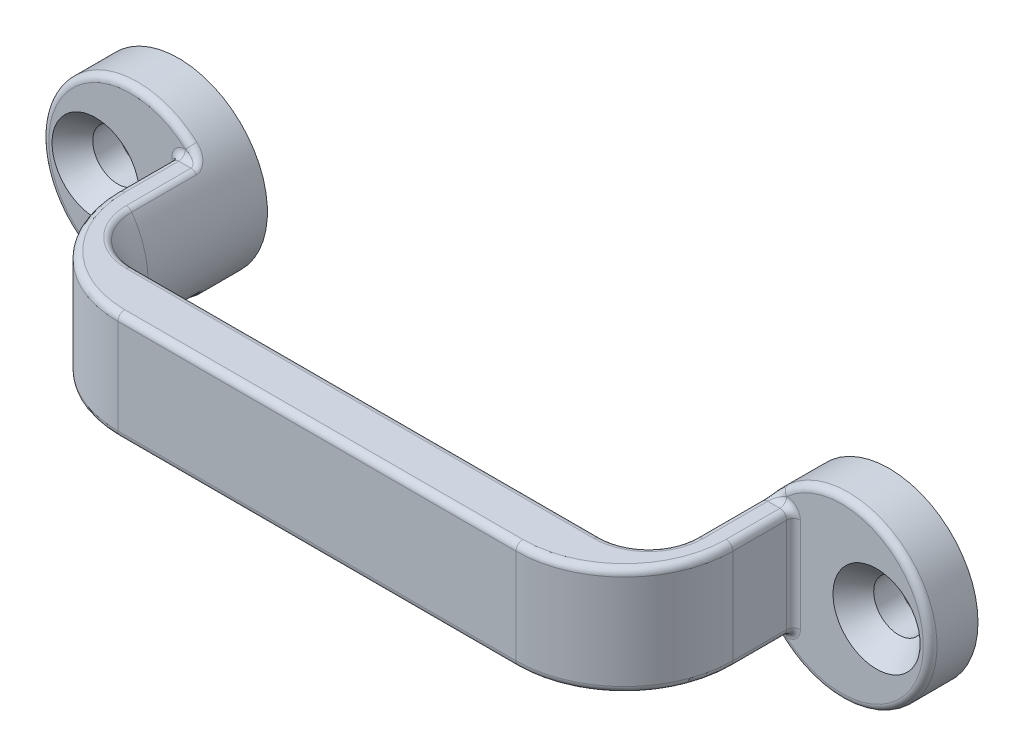
SolidWorks part; units mm, degrees
ref_plane "Front Plane" through (0, 0, 0) normal (0, 0, 1) x (1, 0, 0)
ref_plane "Top Plane" through (0, 0, 0) normal (0, 1, 0) x (1, 0, 0)
ref_plane "Right Plane" through (0, 0, 0) normal (1, 0, 0) x (0, 0, -1)
sketch "Sketch1" plane through (0, 0, 0) normal (0, 0, 1) x (1, 0, 0)
  line L0 (-28.575, 0) -> (28.575, 0) construction
  line L1 (26, 0) -> (-26, 0) construction
  line L2 (0, 3.9688) -> (0, -3.9688)
  circle A0 centre (-28.575, 0) radius 1.6383
  circle A1 centre (28.575, 0) radius 1.6383
  circle A2 centre (26, 0) radius 6.5
  circle A3 centre (-26, 0) radius 6.5
  dimension "Screw Size" = 3.2766
  dimension "Base Dia" = 13
  dimension "A" = 57.15
  dimension "Overall" = 65
  dimension "Height" = 7.9375
sketch "Sketch2" plane through (0, 0, 0) normal (0, 1, 0) x (1, 0, 0)
  line L0 (-19.5, 0) -> (-19.5, -8.7312)
  line L1 (-17.1188, -11.1125) -> (17.1188, -11.1125)
  line L2 (19.5, -8.7312) -> (19.5, 0)
  line L3 (-22.5, 0) -> (-22.5, -7.9375)
  line L4 (-14.5625, -15.875) -> (14.5625, -15.875)
  line L5 (22.5, -7.9375) -> (22.5, 0)
  line L6 (0, 0) -> (0, -15.875) construction
  line L7 (-28.575, 0) -> (28.575, 0) construction
  line L8 (-32.5, 0) -> (-19.5, 0) construction
  line L9 (19.5, 0) -> (32.5, 0) construction
  line L10 (-22.5, 0) -> (-19.5, 0)
  line L11 (19.5, 0) -> (22.5, 0)
  arc A0 (-22.5, -7.9375) -> (-14.5625, -15.875) centre (-14.5625, -7.9375) ccw
  arc A1 (14.5625, -15.875) -> (22.5, -7.9375) centre (14.5625, -7.9375) ccw
  arc A2 (-19.5, -8.7312) -> (-17.1188, -11.1125) centre (-17.1188, -8.7312) ccw
  arc A3 (17.1188, -11.1125) -> (19.5, -8.7312) centre (17.1188, -8.7312) ccw
  point P18 (-22.5, -15.875)
  point P23 (22.5, -15.875)
  dimension "D4" = 7.9375
  dimension "D5" = 2.3813
  dimension "Projection" = 15.875
  dimension "Handle lenght" = 44.9999
  dimension "Width" = 4.7625
extrude "Extrude1" add sketch "Sketch2" against normal up to vertex (3.9688 mm away) and the other way up to vertex (3.9688 mm away) up to point (0, -3.9688, 0) other way up to point (0, 3.9688, 0)
sketch "Sketch6" plane through (0, 0, 0) normal (0, 0, -1) x (-1, 0, 0)
  line L0 (19.5, -3.9688) -> (22.5, -3.9688) construction
  line L1 (19.5, 3.9688) -> (22.5, 3.9688) construction
  line L2 (17.8523, -3.9688) -> (20.8523, -3.9687)
  line L3 (17.8523, 3.9688) -> (20.8523, 3.9688)
  line L4 (17.8523, 3.9688) -> (17.8523, -3.9688)
  circle A0 centre (26, 0) radius 6.5 construction
  arc A1 (20.8523, 3.9688) -> (20.8523, -3.9687) centre (26, 0) ccw
  dimension "D1" = 3
sketch "Sketch7" plane through (0, 0, 0) normal (0, 1, 0) x (1, 0, 0)
  line L0 (19.5, -8.7312) -> (19.5, 0) construction
  line L1 (-17.1188, -11.1125) -> (17.1188, -11.1125) construction
  line L2 (-19.5, 0) -> (-19.5, -8.7312) construction
  line L3 (19.5, -8.7312) -> (19.5, 0)
  line L4 (-17.1188, -11.1125) -> (17.1188, -11.1125)
  line L5 (-19.5, 0) -> (-19.5, -8.7312)
  line L6 (-28.575, 0) -> (28.575, 0) construction
  arc A0 (17.1188, -11.1125) -> (19.5, -8.7312) centre (17.1188, -8.7312) ccw construction
  arc A1 (-19.5, -8.7312) -> (-17.1188, -11.1125) centre (-17.1188, -8.7312) ccw construction
  arc A2 (17.1188, -11.1125) -> (19.5, -8.7312) centre (17.1188, -8.7312) ccw
  arc A3 (-19.5, -8.7312) -> (-17.1188, -11.1125) centre (-17.1188, -8.7312) ccw
sweep "Cut-Sweep2" cut profiles "Sketch6" path "Sketch7"
sketch "Sketch8" plane through (0, 0, 0) normal (0, 0, 1) x (1, 0, 0)
  circle A0 centre (26, 0) radius 6.5 construction
  circle A1 centre (28.575, 0) radius 1.6383 construction
  circle A2 centre (-28.575, 0) radius 1.6383 construction
  circle A3 centre (-26, 0) radius 6.5 construction
  circle A4 centre (26, 0) radius 6.5
  circle A5 centre (28.575, 0) radius 1.6383
  circle A6 centre (-28.575, 0) radius 1.6383
  circle A7 centre (-26, 0) radius 6.5
extrude "Extrude5" add sketch "Sketch8" along normal blind 3.4976
sketch "Sketch9" plane through (0, 0, 3.4976) normal (0, 0, 1) x (1, 0, 0)
  circle A0 centre (-28.575, 0) radius 3.1877
  circle A1 centre (28.575, 0) radius 3.1877
  dimension "cc hole" = 6.3754
extrude "Extrude6" cut sketch "Sketch9" against normal through all draft 40
fillet "Fillet1" radius 0.5 28 edges at (20.1751, -3.9688, 13.5502) (32.5, 0, 3.4976) (21.6761, 3.9688, 3.4976) (22.5, 0, 3.4976) (21.6761, -3.9688, 3.4976) (-22.5, 3.9688, 5.7175) (-22.5, -3.9688, 5.7175) (-22.5, 0, 3.4976) (-21.6761, 3.9688, 3.4976) (-32.5, 0, 3.4976) (-21.6761, -3.9688, 3.4976) (22.5, -3.9688, 5.7175) (-20.1751, 3.9688, 13.5502) (0, 3.9688, 15.875) (20.1751, 3.9688, 13.5502) (22.5, 3.9688, 5.7175) (-20.1751, -3.9688, 13.5502) (0, -3.9688, 15.875) (20.8523, -3.9687, 6.1144) (0, -3.9687, 12.4648) (-20.8523, 3.9688, 6.1144) (19.7588, -3.9687, 11.3713) (-19.7588, -3.9687, 11.3713) (-19.7588, 3.9688, 11.3713) (0, 3.9688, 12.4648) (19.7588, 3.9688, 11.3713) (20.8523, 3.9688, 6.1144) (-20.8523, -3.9687, 6.1144)
sketch "Sketch11" plane through (0, 0, 0) normal (0, 0, -1) x (-1, 0, 0)
  point P0 (-28.575, 0)
  point P1 (28.575, 0)
hole_wizard "#6 Clearance Hole1" positions "Sketch12" profile "Sketch13" hole size "#6" standard "ANSI Inch" end condition through all
sketch "Sketch12" plane through (0, 0, 0) normal (0, 0, -1) x (-1, 0, 0)
  point P0 (-28.575, 0)
  point P3 (28.575, 0)
sketch "Sketch13" plane through (28.575, 0, 0) normal (1, 0, 0) x (0, 1, 0)
  line L0 (0, 0) -> (0, 15.875)
  line L1 (0, 15.875) -> (1.8288, 15.875)
  line L2 (1.8288, 15.875) -> (1.8288, 0)
  line L5 (1.8288, 0) -> (0, 0)
  line L11 (0, -6.35) -> (0, 107.95) construction
  dimension "Thru Hole Dia." = 3.6576
  dimension "Thru Hole Depth" = 15.875
sketch "Sketch14" plane through (0, 0, 0) normal (0, 1, 0) x (1, 0, 0)
  line L0 (28.575, 0) -> (28.575, -3.4976) construction
  line L1 (25.3873, -3.4976) -> (31.7627, -3.4976) construction
equation "\"D4@Sketch2\" = \"Projection@Sketch2\"/2"
equation "\"D5@Sketch2\" = \"D4@Sketch2\"*.3"
